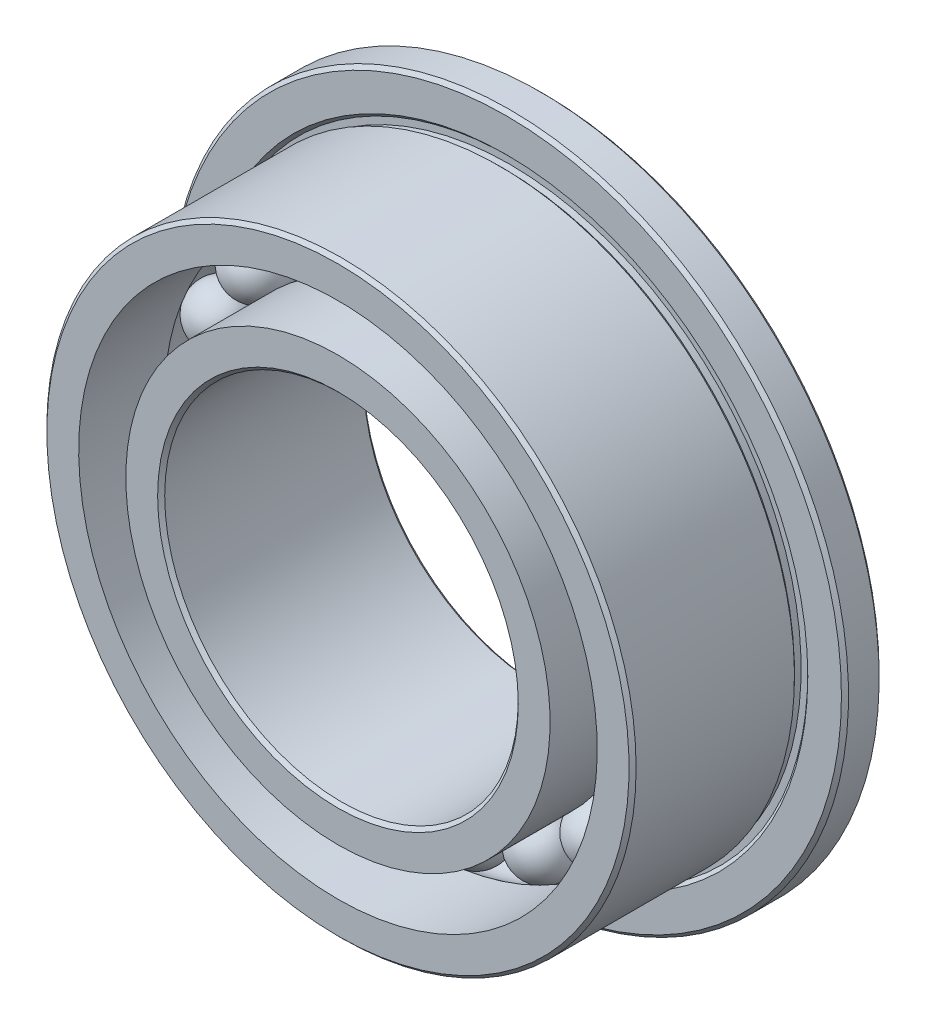
SolidWorks part; units mm, degrees
ref_plane "Front Plane" through (0, 0, 0) normal (0, 0, 1) x (1, 0, 0)
ref_plane "Top Plane" through (0, 0, 0) normal (0, 1, 0) x (1, 0, 0)
ref_plane "Right Plane" through (0, 0, 0) normal (1, 0, 0) x (0, 0, -1)
sketch "Sketch1" plane through (0, 0, 0) normal (1, 0, 0) x (0, 0, -1)
  line L0 (0, 3.9688) -> (0, -3.9688) construction
  line L1 (-1.3891, 3.9688) -> (1.3891, 3.9688) construction
  line L2 (0, 0) -> (1.3891, 0) construction
  line L3 (1.3891, 4.5593) -> (1.3891, -4.5593) construction
  line L4 (1.3891, -4.5593) -> (0.8811, -4.5593) construction
  line L5 (1.3891, 2.3813) -> (0, 2.3813) construction
  line L6 (1.3891, 2.3813) -> (1.3891, -2.3813) construction
  dimension "OD" = 7.9375
  dimension "Width" = 2.7781
  dimension "Flange Dia." = 9.1186
  dimension "Flange Thickness" = 0.508
  dimension "ID" = 4.7625
sketch "Sketch2" plane through (0, 0, 0) normal (1, 0, 0) x (0, 0, -1)
  line L0 (1.3891, 4.5593) -> (0.8811, 4.5593)
  line L1 (0.8811, 4.5593) -> (0.8811, 4.0586)
  line L2 (0.7913, 3.9688) -> (-1.3891, 3.9688)
  line L3 (-1.3891, 3.9688) -> (-1.3891, 3.4925)
  line L4 (-1.3891, 3.4925) -> (-0.2381, 3.4925)
  line L5 (1.3891, 4.5593) -> (1.3891, -4.5593) construction
  line L6 (1.3891, 3.4925) -> (1.3891, 4.5593)
  line L7 (1.3891, 2.3813) -> (-1.3891, 2.3813)
  line L8 (-1.3891, 2.3813) -> (-1.3891, 2.8575)
  line L9 (-1.3891, 2.8575) -> (-0.2381, 2.8575)
  line L10 (1.3891, 2.8575) -> (1.3891, 2.3813)
  line L11 (0, 3.9688) -> (0, 2.3813) construction
  line L12 (-0.3969, 3.175) -> (0.3969, 3.175) construction
  line L13 (0.2381, 3.4925) -> (1.3891, 3.4925)
  line L14 (0.2381, 2.8575) -> (1.3891, 2.8575)
  line L15 (0.8811, 4.0586) -> (0.926, 4.0137)
  line L16 (0.926, 4.0137) -> (0.926, 3.9238)
  line L17 (0.926, 3.9238) -> (0.8362, 3.9238)
  line L18 (0.8362, 3.9238) -> (0.7913, 3.9688)
  line L19 (0.8811, 3.9687) -> (0.926, 3.9238) construction
  line L20 (0.926, 4.0137) -> (0.8362, 3.9238) construction
  line L21 (0.7913, 3.9688) -> (0.8811, 3.9687) construction
  line L22 (0.8811, 3.9687) -> (0.8811, 4.0586) construction
  circle A0 centre (0, 3.175) radius 0.3969 construction
  arc A1 (-0.2381, 3.4925) -> (0.2381, 3.4925) centre (0, 3.175) cw
  arc A2 (-0.2381, 2.8575) -> (0.2381, 2.8575) centre (0, 3.175) ccw
  dimension "D1" = 1.5875
  dimension "Ball Dia." = 0.7937
  dimension "D2" = 135
  dimension "D3" = 0.127
  dimension "D4" = 0.635
  dimension "Race Thickness" = 0.4762
revolve "Revolve1" add sketch "Sketch2" angle 360 about L2
fillet "Fillet1" radius 0.0476 3 edges at (0, -4.5593, -1.3891) (0, -4.5593, -0.8811) (0, -3.9688, 1.3891) profile chamfer
sketch "Sketch3" plane through (0, 0, 0) normal (0, 0, 1) x (1, 0, 0)
  line L0 (-2.3813, 0) -> (2.3813, 0) construction
  line L1 (-3.9688, 0) -> (3.9688, 0) construction
  point P5 (0, 0)
  dimension "ID2" = 4.7625
  dimension "OD2" = 7.9375
fillet "Fillet2" radius 0.0476 2 edges at (0, -2.3813, -1.3891) (0, -2.3813, 1.3891) profile chamfer
sketch "Sketch7" plane through (0, 0, 0) normal (0, 0, 1) x (1, 0, 0)
  line L0 (0, 3.5719) -> (0, 2.7781)
  line L1 (0, 4.5593) -> (0, -4.5593) construction
  line L2 (-0.45, 3.5719) -> (0, 0) construction
  line L3 (0, 0) -> (0.45, 3.5719) construction
  line L4 (0.45, 3.5719) -> (-0.45, 3.5719) construction
  circle A0 centre (0, 3.175) radius 0.3969 construction
  circle A1 centre (0, 0) radius 3.5719 construction
  circle A2 centre (0, 0) radius 2.7781 construction
  arc A4 (0, 3.5719) -> (0, 2.7781) centre (0, 3.175) ccw
  dimension "D1" = 14.362
revolve "Revolve3" add sketch "Sketch7" angle 360 about L0
pattern_circular "CirPattern3" count 21 over 360 about axis through (0, 0, 0) along (0, 0, -1) of bodies 107
sketch "Sketch8" [suppressed] plane through (0, 0, 0) normal (1, 0, 0) x (0, 0, -1)
  line L1 (-1.1906, 2.0241) -> (-1.0477, 2.0241)
  line L2 (-1.1906, 2.0241) -> (-1.1906, 2.1431)
  line L3 (-1.1906, 2.1431) -> (-1.0477, 2.1431)
  line L4 (-1.0477, 2.0241) -> (-1.0477, 2.1431)
  line L5 (1.1906, 2.0241) -> (1.0478, 2.0241)
  line L6 (1.1906, 2.0241) -> (1.1906, 2.1431)
  line L7 (1.1906, 2.1431) -> (1.0478, 2.1431)
  line L8 (1.0478, 2.0241) -> (1.0478, 2.1431)
  line L9 (1.1906, 1.5478) -> (1.0478, 1.5478)
  line L10 (1.1906, 1.5478) -> (1.1906, 1.4287)
  line L11 (1.1906, 1.4287) -> (1.0478, 1.4287)
  line L12 (1.0478, 1.5478) -> (1.0478, 1.4287)
  line L13 (-1.1906, 1.5478) -> (-1.0477, 1.5478)
  line L14 (-1.1906, 1.5478) -> (-1.1906, 1.4287)
  line L15 (-1.1906, 1.4287) -> (-1.0477, 1.4287)
  line L16 (-1.0477, 1.5478) -> (-1.0477, 1.4287)
  dimension "D1" = 0.1587
  dimension "D2" = 0.1905
revolve "Cut-Revolve1" [suppressed] cut sketch "Sketch8" angle 360 about L2
sketch "Sketch9" [suppressed] plane through (0, 0, 0) normal (1, 0, 0) x (0, 0, -1)
  line L0 (-1.0477, 2.1431) -> (-1.0477, 1.8657)
  line L1 (-1.0477, 1.8657) -> (-1.1192, 1.7419)
  line L2 (-1.1192, 1.7419) -> (-1.1192, 1.4645)
  line L3 (1.1192, 1.4645) -> (1.1192, 1.4287) construction
  line L4 (1.0478, 2.1431) -> (1.0478, 1.8657)
  line L5 (1.0478, 1.8657) -> (1.1192, 1.7419)
  line L6 (1.1192, 1.7419) -> (1.1192, 1.4645)
  line L7 (1.1906, 1.4287) -> (1.0478, 1.4287) construction
  line L8 (-1.0835, 2.1431) -> (-1.0835, 1.8752)
  line L9 (-1.0835, 1.8752) -> (-1.1549, 1.7515)
  line L10 (-1.1549, 1.7515) -> (-1.1549, 1.4645)
  line L11 (-1.0477, 2.1431) -> (-1.0835, 2.1431)
  line L12 (-1.1192, 1.4645) -> (-1.1549, 1.4645)
  line L13 (1.0835, 2.1431) -> (1.0835, 1.8752)
  line L14 (1.0835, 1.8752) -> (1.1549, 1.7515)
  line L15 (1.1549, 1.7515) -> (1.1549, 1.4645)
  line L16 (1.0478, 2.1431) -> (1.0835, 2.1431)
  line L17 (1.1192, 1.4645) -> (1.1549, 1.4645)
  line L18 (-1.0477, 1.8657) -> (-1.0477, 2.6) construction
  line L19 (1.0478, 1.8657) -> (1.0478, 2.1431) construction
  line L20 (-1.0477, 1.4287) -> (-1.1906, 1.4287) construction
  line L22 (-1.1192, 1.4645) -> (-1.1192, 1.4287) construction
  dimension "D2" = 150
  dimension "D1" = 150
  dimension "D5" = 0.1429
  dimension "D3" = 0.0357
  dimension "D4" = 0.0357
revolve "Revolve4" [suppressed] add sketch "Sketch9" angle 360 about L2
ref_axis "Center Axis 1" through (0, 0, -0.8731) along (0, 0, 1)
ref_plane "Contact Plane 1" through (0, 0, -0.8811) normal (0, 0, 1) x (1, 0, 0)
equation "\"Ball Dia.@Sketch2\"=\"D1@Sketch2\"*.5"
equation "\"D3@Sketch2\"=\"Flange Thickness@Sketch1\"/4"
equation "\"D1@Fillet1\"=\"Race Thickness@Sketch2\"/10"
equation "\"ID2@Sketch3\" = \"ID@Sketch1\""
equation "\"OD2@Sketch3\" = \"OD@Sketch1\""
equation "\"D1@Fillet2\"=\"Race Thickness@Sketch2\"/10"
equation "\"D1@CirPattern3\"=360/\"D1@Sketch7\"-4"
equation "\"D1@Sketch8\"=\"Race Thickness@Sketch2\"/3"
equation "\"D2@Sketch8\"=\"Race Thickness@Sketch2\"/2.5"
equation "\"D3@Sketch9\"=\"D5@Sketch9\"/4"
equation "\"D4@Sketch9\"=\"D5@Sketch9\"/4"
equation "\"D1@Sketch9\"=\"D2@Sketch9\""
equation "\"D4@Sketch2\"=\"D1@Sketch2\"*.4"
